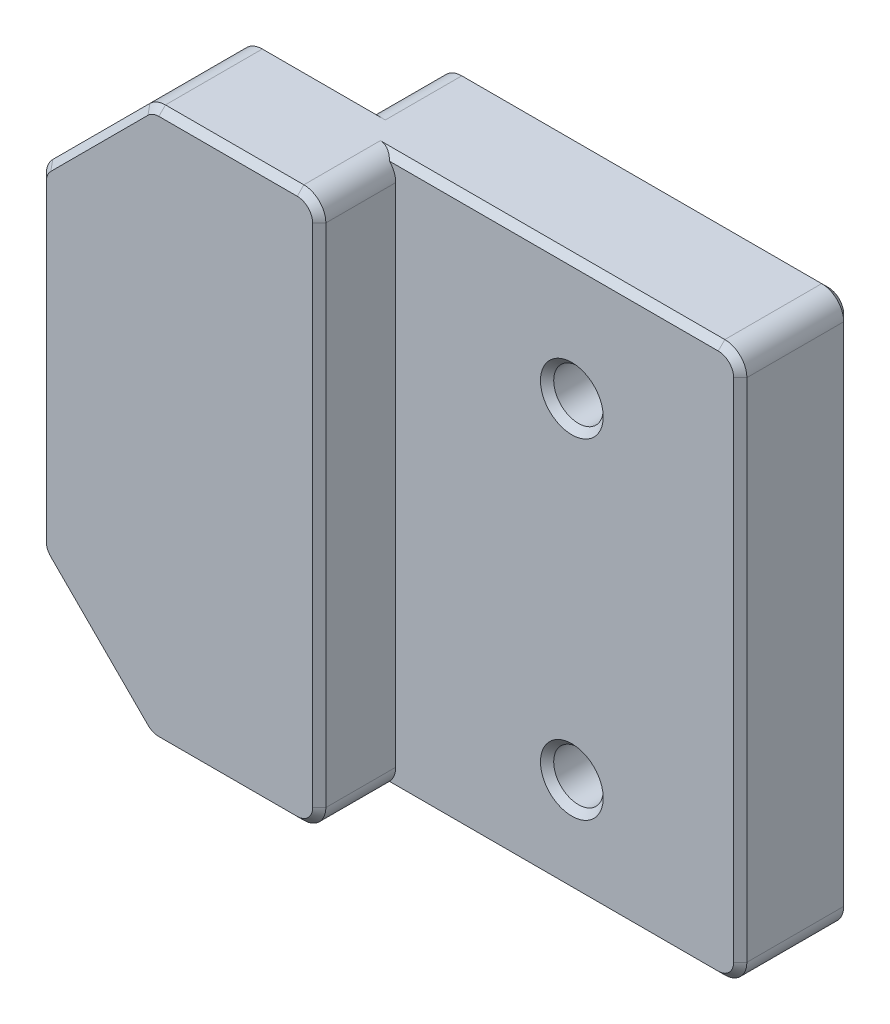
SolidWorks part; units mm, degrees
ref_plane "Front Plane" through (0, 0, 0) normal (0, 0, 1) x (1, 0, 0)
ref_plane "Top Plane" through (0, 0, 0) normal (0, 1, 0) x (1, 0, 0)
ref_plane "Right Plane" through (0, 0, 0) normal (1, 0, 0) x (0, 0, -1)
sketch "Sketch1" plane through (0, 0, 0) normal (0, 1, 0) x (1, 0, 0)
  line L0 (0, 0) -> (-18.35, 0)
  line L1 (-18.35, 0) -> (-18.35, -3.475)
  line L2 (-18.35, -3.475) -> (-28.35, -3.475)
  line L3 (-28.35, -3.475) -> (-28.35, -8.475)
  line L4 (-28.35, -8.475) -> (-15.65, -8.475)
  line L5 (-15.65, -8.475) -> (-15.65, -5)
  line L6 (-15.65, -5) -> (0, -5)
  line L7 (0, -5) -> (0, 0)
  dimension "D1" = 5
  dimension "D2" = 2.7
  dimension "D3" = 18.35
  dimension "D4" = 10
  dimension "D5" = 3.475
  dimension "D6" = 5
extrude "Boss-Extrude1" add sketch "Sketch1" along normal blind 25
sketch "Sketch2" plane through (0, 0, 5) normal (0, 0, 1) x (1, 0, 0)
  line L0 (-7.65, 4.5) -> (-7.65, 19.5) construction
  line L1 (-15.65, 0) -> (0, 0) construction
  line L2 (0, 25) -> (0, 0) construction
  circle A0 centre (-7.65, 4.5) radius 1.125
  circle A1 centre (-7.65, 19.5) radius 1.125
  dimension "D1" = 2.25
  dimension "D2" = 4.5
  dimension "D3" = 7.65
  dimension "D4" = 15
extrude "Cut-Extrude1" cut sketch "Sketch2" against normal blind 25
chamfer "Chamfer1" distance 5 angle 45 2 edges at (-28.35, 0, 5.975) (-28.35, 25, 5.975)
fillet "Fillet1" radius 1 10 edges at (0, 0, 2.5) (-28.35, 20, 5.975) (-15.65, 25, 6.7375) (-15.65, 0, 6.7375) (-23.35, 0, 5.975) (-28.35, 5, 5.975) (-23.35, 25, 5.975) (0, 25, 2.5) (-18.35, 25, 1.7375) (-18.35, 0, 1.7375)
chamfer "Chamfer2" distance 0.3 angle 45 38 edges at (-6.525, 4.5, 0) (-6.525, 19.5, 0) (-6.525, 4.5, 5) (-6.525, 19.5, 5) (-9.175, 0, 0) (-0.2929, 0.2929, 0) (0, 12.5, 0) (-0.2929, 24.7071, 0) (-9.175, 25, 0) (-28.35, 12.5, 8.475) (-28.2739, 19.9685, 8.475) (-28.2739, 5.0315, 8.475) (-25.85, 22.5, 8.475) (-25.85, 2.5, 8.475) (-23.3185, 24.9239, 8.475) (-23.3185, 0.0761, 8.475) (-19.7929, 25, 8.475) (-19.7929, 0, 8.475) (-15.9429, 24.7071, 8.475) (-15.9429, 0.2929, 8.475) (-15.65, 12.5, 8.475) (-18.0571, 0.2929, 0) (-18.35, 12.5, 0) (-18.0571, 24.7071, 0) (-8.825, 25, 5) (-8.825, 0, 5) (-0.2929, 24.7071, 5) (-0.2929, 0.2929, 5) (0, 12.5, 5) (-20.1429, 0, 3.475) (-23.3185, 0.0761, 3.475) (-25.85, 2.5, 3.475) (-28.2739, 5.0315, 3.475) (-28.35, 12.5, 3.475) (-20.1429, 25, 3.475) (-28.2739, 19.9685, 3.475) (-23.3185, 24.9239, 3.475) (-25.85, 22.5, 3.475)
